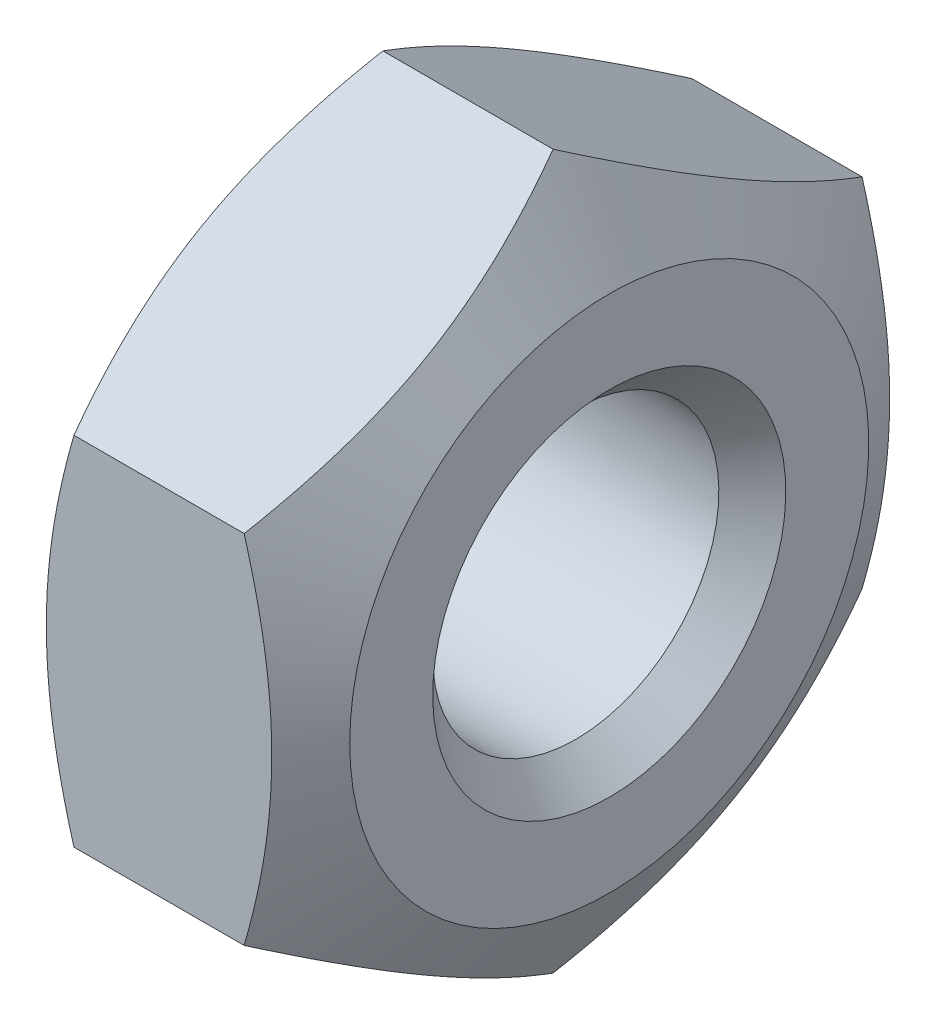
SolidWorks part; units mm, degrees
ref_plane "前视基准面" through (0, 0, 0) normal (0, 0, 1) x (1, 0, 0)
ref_plane "上视基准面" through (0, 0, 0) normal (0, 1, 0) x (1, 0, 0)
ref_plane "右视基准面" through (0, 0, 0) normal (1, 0, 0) x (0, 0, -1)
ref_plane "基准面1" through (0, 0, 0) normal (1, 0, 0) x (0, 0, -1)
sketch "草图1" plane through (0, 0, 0) normal (1, 0, 0) x (0, 0, -1)
  line L0 (-3.5, -2.0207) -> (0, -4.0415)
  line L1 (0, -4.0415) -> (3.5, -2.0207)
  line L2 (3.5, -2.0207) -> (3.5, 2.0207)
  line L3 (3.5, 2.0207) -> (0, 4.0415)
  line L4 (0, 4.0415) -> (-3.5, 2.0207)
  line L5 (-3.5, 2.0207) -> (-3.5, -2.0207)
extrude "凸台-拉伸1" add sketch "草图1" against normal blind 1.6 and the other way blind 1.6
ref_plane "基准面2" through (0, 0, 0) normal (0, 0, 1) x (1, 0, 0)
sketch "草图2" plane through (0, 0, 0) normal (0, 0, 1) x (1, 0, 0)
  line L0 (-1.6, 0) -> (-1.6, 2)
  line L1 (-1.6, 2) -> (-1.221, 1.621)
  line L2 (-1.221, 1.621) -> (1.221, 1.621)
  line L3 (1.221, 1.621) -> (1.6, 2)
  line L4 (1.6, 2) -> (1.6, 0)
  line L5 (1.6, 0) -> (-1.6, 0)
  line L6 (1.6, 0) -> (-1.6, 0) construction
revolve "切除-旋转1" cut sketch "草图2" angle 360 about L6 reverse direction yes
cosmetic thread "装饰螺纹线1" parameters "D1"=3.2, "D2"=4
ref_plane "基准面3" through (0, 0, 0) normal (0, 0, 1) x (1, 0, 0)
sketch "草图3" plane through (0, 0, 0) normal (0, 0, 1) x (1, 0, 0)
  line L0 (-6.6, 6.94) -> (-6.6, 1)
  line L1 (-6.6, 1) -> (-1.6, 1)
  line L2 (-1.6, 1) -> (-1.6, 2.94)
  line L3 (-1.6, 2.94) -> (0, 5.7113)
  line L4 (0, 5.7113) -> (1.6, 2.94)
  line L5 (1.6, 2.94) -> (1.6, 1)
  line L6 (1.6, 1) -> (6.6, 1)
  line L7 (6.6, 1) -> (6.6, 6.94)
  line L8 (6.6, 6.94) -> (-6.6, 6.94)
  line L9 (50, 0) -> (-50, 0) construction
revolve "切除-旋转2" cut sketch "草图3" angle 360 about L9 reverse direction yes
